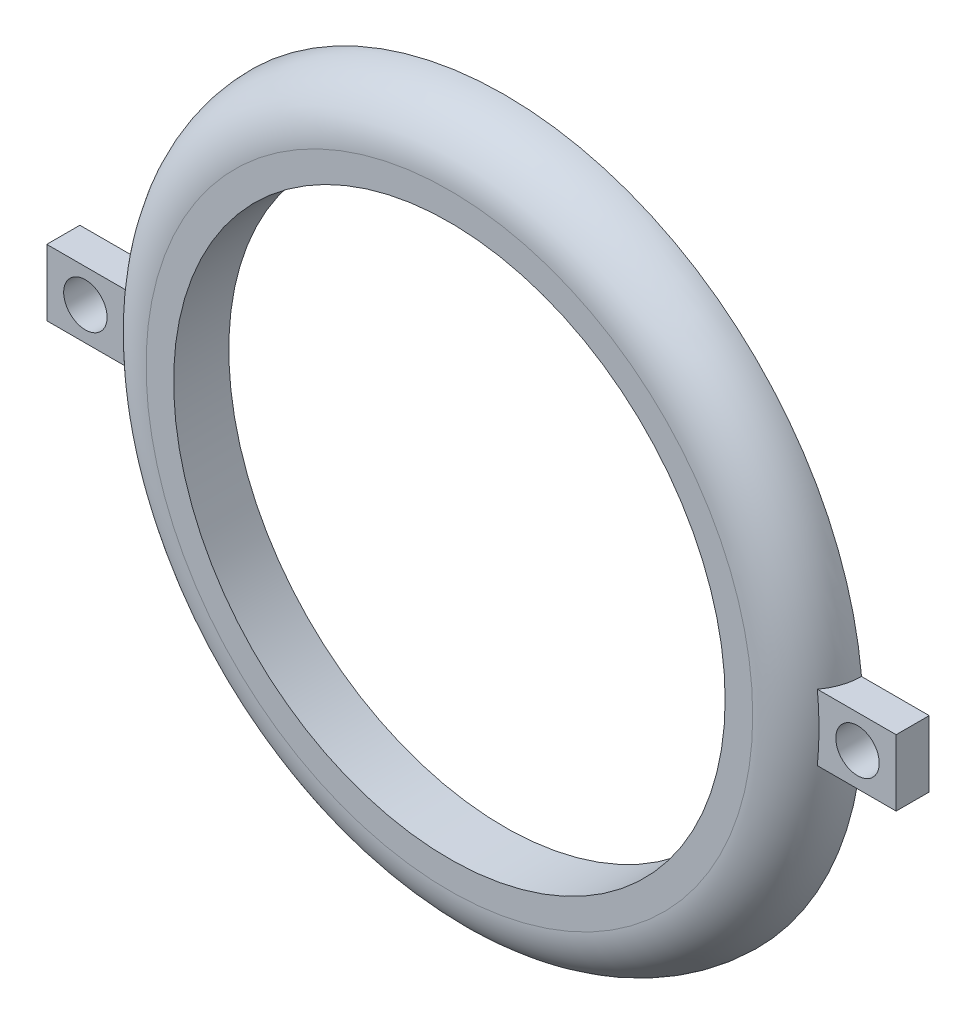
SolidWorks part; units mm, degrees
ref_plane "Front Plane" through (0, 0, 0) normal (0, 0, 1) x (1, 0, 0)
ref_plane "Top Plane" through (0, 0, 0) normal (0, 1, 0) x (1, 0, 0)
ref_plane "Right Plane" through (0, 0, 0) normal (1, 0, 0) x (0, 0, -1)
sketch "Sketch1" plane through (0, 0, 0) normal (0, 0, 1) x (1, 0, 0)
  circle A0 centre (0, 0) radius 16.51
  circle A1 centre (0, 0) radius 12.7
  dimension "D1" = 33.02
  dimension "D2" = 25.4
extrude "Boss-Extrude1" add sketch "Sketch1" along normal blind 2.54
ref_plane "Plane1" through (-16.51, 0, 0) normal (-1, 0, 0) x (0, 0, 1)
sketch "Sketch4" plane through (-16.51, 0, 0) normal (-1, 0, 0) x (0, 0, 1)
  line L0 (0, -1.524) -> (0, 1.524)
  line L1 (0, 16.51) -> (0, -16.51) construction
  line L2 (0, 1.524) -> (1.524, 1.524)
  line L3 (1.524, 1.524) -> (1.524, -1.524)
  line L4 (1.524, -1.524) -> (0, -1.524)
  point P5 (0, 0)
  dimension "D1" = 1.524
  dimension "D2" = 3.048
extrude "Boss-Extrude2" add sketch "Sketch4" against normal up to surface and the other way blind 3.048 up to face at (16.51, 0, 2.54)
mirror "Mirror2" about plane through (0, 0, 0) normal (1, 0, 0) of "Boss-Extrude2"
fillet "Fillet3" radius 2.54 1 edges at (16.51, 0, 2.54)
sketch "Sketch5" plane through (0, 0, 1.524) normal (0, 0, 1) x (1, 0, 0)
  circle A0 centre (-17.78, 0) radius 1
  circle A1 centre (0, 0) radius 17.78 construction
  point P4 (0, 0)
  point P5 (0, 0)
  dimension "D1" = 2
  dimension "D2" = 35.56
extrude "Cut-Extrude1" cut sketch "Sketch5" against normal blind 2.54
mirror "Mirror3" about plane through (0, 0, 0) normal (1, 0, 0) of "Cut-Extrude1"
